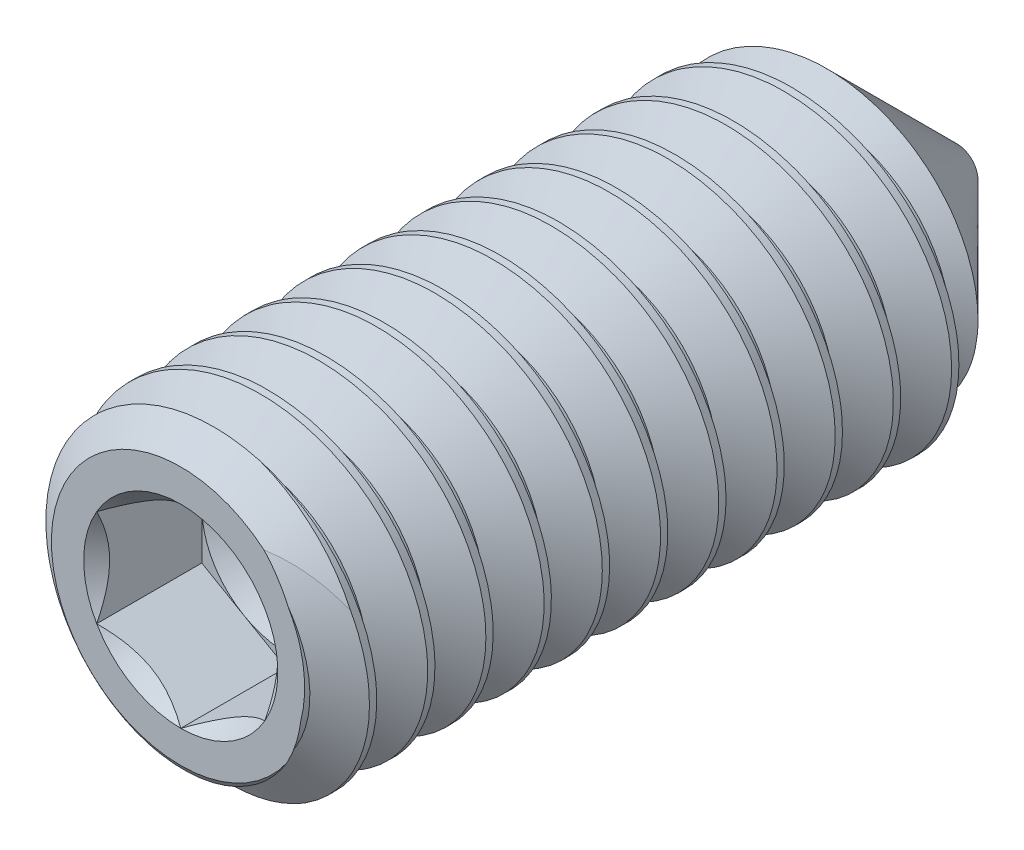
SolidWorks part; units mm, degrees
ref_plane "Front" through (0, 0, 0) normal (0, 0, 1) x (1, 0, 0)
ref_plane "Top" through (0, 0, 0) normal (0, 1, 0) x (1, 0, 0)
ref_plane "Right" through (0, 0, 0) normal (1, 0, 0) x (0, 0, -1)
sketch "Body Sketch" plane through (0, 0, 0) normal (1, 0, 0) x (0, 0, -1)
  line L0 (-3, 0) -> (-3, 1)
  line L1 (-3, 1) -> (-2.8249, 1.25)
  line L2 (-2.8249, 1.25) -> (1.9125, 1.25)
  line L3 (1.9125, 1.25) -> (3, 0.1625)
  line L4 (-3, 1) -> (-3, -1) construction
  line L5 (3, 0) -> (-3, 0)
  line L6 (0, 1.25) -> (0, -1.25) construction
  line L8 (3, 0.1625) -> (3, 0)
  line L9 (-3, -1.25) -> (3, -1.25) construction
  line L10 (3, 0.1625) -> (3, -0.1625) construction
  line L11 (3, -0.1625) -> (1.9125, -1.25) construction
  line L13 (3, 0.1625) -> (2.8375, 0) construction
  line L15 (2.8375, 0) -> (3, -0.1625) construction
  dimension "D3" = 35
  dimension "D7" = 2
  dimension "Diameter" = 2.5
  dimension "Length" = 6
  dimension "D2" = 0.325
  dimension "Cone Angle" = 90
  dimension "D90" = 90
revolve "Body Revolve" add sketch "Body Sketch" angle 360 about L5
ref_plane "Plane1" through (0, 0, -3) normal (0, 0, 1) x (1, 0, 0)
sketch "Spiral Sketch" plane through (0, 0, -3) normal (0, 0, 1) x (1, 0, 0)
  circle A0 centre (0, 0) radius 1.25 construction
  circle A1 centre (0, 0) radius 1.25
sketch "Hex Sketch" plane through (0, 0, 3) normal (0, 0, 1) x (1, 0, 0)
  line L1 (0, 0.7506) -> (-0.65, 0.3753)
  line L2 (-0.65, 0.3753) -> (-0.65, -0.3753)
  line L3 (-0.65, -0.3753) -> (0, -0.7506)
  line L4 (0, -0.7506) -> (0.65, -0.3753)
  line L5 (0.65, -0.3753) -> (0.65, 0.3753)
  line L6 (0.65, 0.3753) -> (0, 0.7506)
  circle A0 centre (0, 0) radius 0.65 construction
  dimension "Hex" = 1.3
extrude "Hex Extrude" cut sketch "Hex Sketch" against normal blind 0.8125
sketch "Hex Entry Sketch" plane through (0, 0, 3) normal (0, 0, 1) x (1, 0, 0)
  circle A0 centre (0, 0) radius 0.7506
extrude "Hex Entry Extrude" cut sketch "Hex Entry Sketch" against normal through all draft 45
sketch "Hex Bottom Sketch" plane through (0, 0, 2.1875) normal (0, 0, 1) x (1, 0, 0)
  circle A0 centre (0, 0) radius 0.65 construction
  circle A1 centre (0, 0) radius 0.65
extrude "Hex Bottom Extrude" cut sketch "Hex Bottom Sketch" against normal through all draft 60
curve "Helix/Spiral" pitch 0.45 height 6.45 radius 1.25 centre (0, 0, -3) axis (0, 0, 1) start towards (0, 1, 0)
sketch "Sketch28" plane through (0, 0, 0) normal (1, 0, 0) x (0, 0, -1)
  line L0 (3, 1.25) -> (3.3938, 1.25)
  line L1 (3.3938, 1.25) -> (3.225, 0.9577)
  line L2 (3.225, 0.9577) -> (3.1688, 0.9577)
  line L3 (3.1688, 0.9577) -> (3, 1.25)
  line L4 (3.0844, 1.1039) -> (3.3094, 1.1039) construction
  line L6 (-2.8249, 1.25) -> (1.9125, 1.25) construction
  line L7 (3, 6.7518) -> (3, -6.7518) construction
  dimension "D1" = 0.0563
  dimension "D3" = 60
  dimension "D2" = 0.225
sweep "Thread Sweep" cut profiles "Sketch28" path "Helix/Spiral"
ref_plane "Contact Plane 1" through (0, 0, 3) normal (0, 0, 1) x (1, 0, 0)
ref_plane "Contact Plane 2" through (0, 0, -3) normal (0, 0, -1) x (-1, 0, 0)
ref_axis "Center Axis 1" through (0, 0, 48.3835) along (0, 0, -1)
equation "\"D7@Body Sketch\" = \"Diameter@Body Sketch\" * .8"
equation "\"D1@Sketch28\" = \"D4@Helix/Spiral\" * .125"
equation "\"D3@Helix/Spiral\" = \"Length@Body Sketch\" + \"D4@Helix/Spiral\""
equation "\"hex Depth@Hex Extrude\" = \"Hex@Hex Sketch\" * .625"
equation "\"D2@Sketch28\" = \"D4@Helix/Spiral\" * .5"
equation "\"D2@Body Sketch\" = \"Diameter@Body Sketch\" * .13"
equation "\"D90@Body Sketch\" = \"Cone Angle@Body Sketch\""
equation "\"Diameter\"= 2.5mm"
equation "\"Thread Pitch\"= 0.45mm"
equation "\"Hex Size\"= 1.3mm"
equation "\"Diameter@Body Sketch\" = \"Diameter\""
equation "\"Hex@Hex Sketch\" = \"Hex Size\""
equation "\"D4@Helix/Spiral\"=\"Thread Pitch\""
